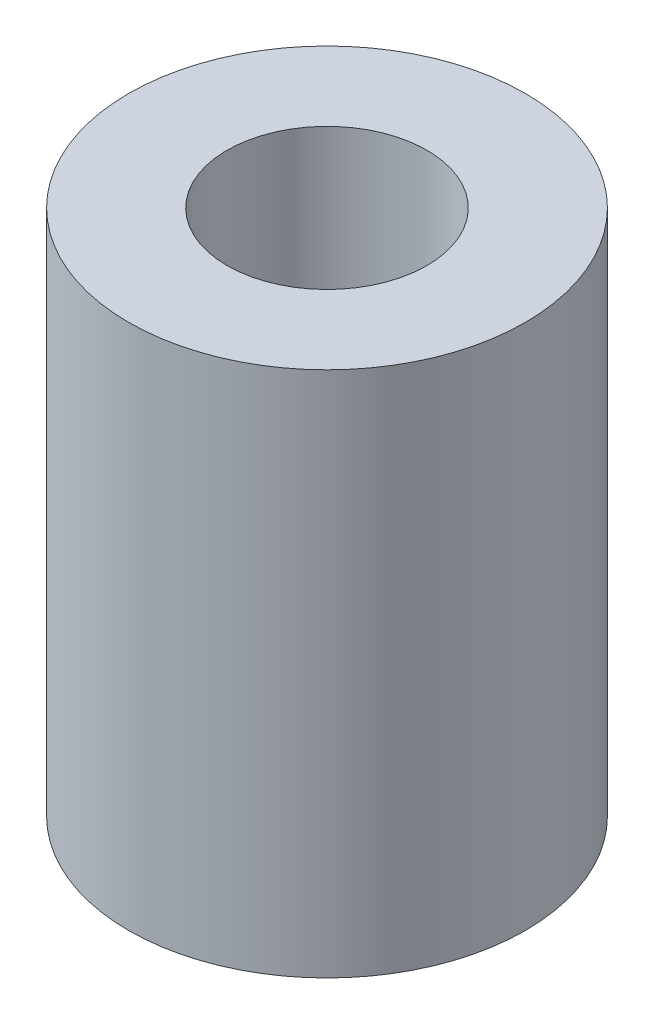
SolidWorks part; units mm, degrees
ref_plane "Front Plane" through (0, 0, 0) normal (0, 0, 1) x (1, 0, 0)
ref_plane "Top Plane" through (0, 0, 0) normal (0, 1, 0) x (1, 0, 0)
ref_plane "Right Plane" through (0, 0, 0) normal (1, 0, 0) x (0, 0, -1)
sketch "Sketch1" plane through (0, 0, 0) normal (0, 1, 0) x (1, 0, 0)
  circle A0 centre (0, 0) radius 7.9375
  dimension "D1" = 15.875
extrude "Boss-Extrude1" add sketch "Sketch1" along normal blind 21.082
sketch "Sketch2" plane through (0, 21.082, 0) normal (0, 1, 0) x (1, 0, 0)
  circle A0 centre (0, 0) radius 4
  dimension "D1" = 8
sketch "Sketch3" plane through (0, 21.082, 0) normal (0, 1, 0) x (1, 0, 0)
  circle A0 centre (0, 0) radius 4
  dimension "D1" = 8
extrude "Cut-Extrude2" cut sketch "Sketch3" against normal through all
